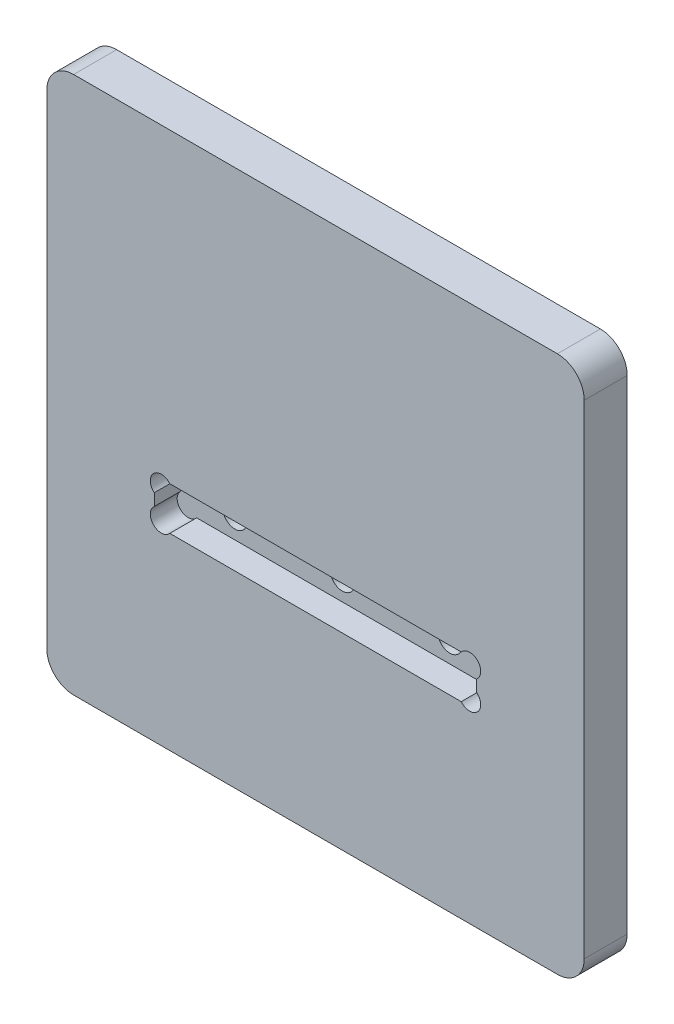
SolidWorks part; units mm, degrees
ref_plane "Front" through (0, 0, 0) normal (0, 0, 1) x (1, 0, 0)
ref_plane "Top" through (0, 0, 0) normal (0, 1, 0) x (1, 0, 0)
ref_plane "Right" through (0, 0, 0) normal (1, 0, 0) x (0, 0, -1)
sketch "Esquisse1" plane through (0, 0, 0) normal (0, 0, 1) x (1, 0, 0)
  line L1 (0, 0) -> (100, 0)
  line L2 (0, 0) -> (0, 100)
  line L3 (0, 100) -> (100, 100)
  line L4 (100, 0) -> (100, 100)
  dimension "D1" = 100
  dimension "D2" = 100
extrude "Boss.-Extru.1" add sketch "Esquisse1" along normal blind 8
sketch "Esquisse2" plane through (0, 0, 8) normal (0, 0, 1) x (1, 0, 0)
  line L1 (20, 43) -> (80, 43)
  line L2 (20, 43) -> (20, 35)
  line L3 (20, 35) -> (80, 35)
  line L4 (80, 43) -> (80, 35)
  line L6 (100, 100) -> (0, 100) construction
  line L7 (50, 35) -> (50, 0) construction
  line L8 (0, 0) -> (100, 0) construction
  dimension "D1" = 8
  dimension "D2" = 57
  dimension "D3" = 60
extrude "Enlèv. mat.-Extru.1" cut sketch "Esquisse2" against normal blind 5
fillet "Congé1" radius 5 4 edges at (100, 0, 4) (0, 0, 4) (0, 100, 4) (100, 100, 4)
sketch "Esquisse3" plane through (0, 0, 8) normal (0, 0, 1) x (1, 0, 0)
  line L0 (80, 43) -> (78.6919, 41.6919) construction
  line L1 (80, 35) -> (80, 43) construction
  line L2 (80, 43) -> (80.1414, 43.1414) construction
  line L3 (50, 43) -> (50, 35) construction
  line L4 (80, 43) -> (20, 43) construction
  line L5 (20, 35) -> (80, 35) construction
  line L6 (80, 35) -> (80, 43) construction
  line L7 (77.1135, 43) -> (80, 40.1135)
  line L8 (50, 39) -> (55.2954, 39) construction
  line L9 (80, 35) -> (80.1414, 34.8586) construction
  line L10 (80, 35) -> (78.6919, 36.3081) construction
  line L11 (77.1135, 35) -> (80, 37.8865)
  line L12 (20, 35) -> (21.3081, 36.3081) construction
  line L13 (20, 35) -> (19.8586, 34.8586) construction
  line L14 (20, 43) -> (19.8586, 43.1414) construction
  line L15 (20, 43) -> (21.3081, 41.6919) construction
  line L16 (22.8865, 35) -> (20, 37.8865)
  line L17 (22.8865, 43) -> (20, 40.1135)
  circle A0 centre (78.6919, 41.6919) radius 2.05 construction
  arc A1 (77.1135, 43) -> (80, 40.1135) centre (78.6919, 41.6919) cw
  circle A2 centre (78.6919, 36.3081) radius 2.05 construction
  arc A3 (77.1135, 35) -> (80, 37.8865) centre (78.6919, 36.3081) ccw
  circle A4 centre (21.3081, 36.3081) radius 2.05 construction
  circle A5 centre (21.3081, 41.6919) radius 2.05 construction
  arc A6 (22.8865, 35) -> (20, 37.8865) centre (21.3081, 36.3081) cw
  arc A7 (22.8865, 43) -> (20, 40.1135) centre (21.3081, 41.6919) ccw
  dimension "D2" = 4.1
  dimension "D1" = 135
  dimension "D3" = 0.2
extrude "Enlèv. mat.-Extru.2" cut sketch "Esquisse3" against normal up to vertex (5 mm away) up to point (20, 35, 3)
sketch "Esquisse4" plane through (0, 0, 3) normal (0, 0, 1) x (1, 0, 0)
  line L0 (20, 39) -> (80, 39) construction
  line L1 (20, 40.1135) -> (20, 37.8865) construction
  line L2 (80, 37.8865) -> (80, 40.1135) construction
  line L3 (50, 39) -> (50, 43) construction
  line L4 (77.1135, 43) -> (22.8865, 43) construction
  circle A0 centre (50, 39) radius 2.25
  circle A1 centre (70, 39) radius 2.25
  circle A2 centre (30, 39) radius 2.25
  dimension "D1" = 20
  dimension "D2" = 4.5
extrude "Enlèv. mat.-Extru.3" cut sketch "Esquisse4" against normal through all both and the other way through all
